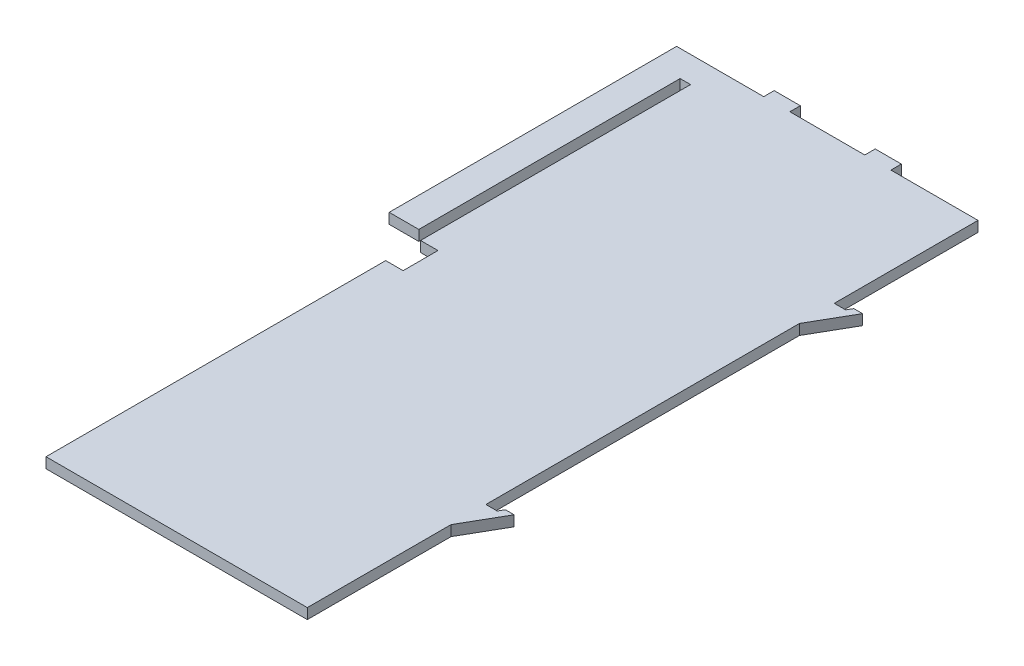
SolidWorks part; units mm, degrees
ref_plane "Front Plane" through (0, 0, 0) normal (0, 0, 1) x (1, 0, 0)
ref_plane "Top Plane" through (0, 0, 0) normal (0, 1, 0) x (1, 0, 0)
ref_plane "Right Plane" through (0, 0, 0) normal (1, 0, 0) x (0, 0, -1)
sketch "Sketch1" plane through (0, 0, 0) normal (0, 1, 0) x (1, 0, 0)
  line L0 (0, 0) -> (0, 165)
  line L3 (173, -220) -> (23, -220)
  line L4 (0, 0) -> (17, 0)
  line L5 (17, 0) -> (17, 150)
  line L6 (17, 150) -> (23, 150)
  line L13 (65, 171) -> (65, 165)
  line L14 (65, 165) -> (108, 165)
  line L15 (108, 165) -> (108, 171)
  line L17 (65, 171) -> (50, 171)
  line L18 (50, 171) -> (50, 165)
  line L19 (50, 165) -> (0, 165)
  line L20 (108, 171) -> (123, 171)
  line L21 (173, 82.5) -> (179.5, 82.5)
  line L22 (123, 171) -> (123, 165)
  line L23 (123, 165) -> (173, 165)
  line L24 (179.5, 82.5) -> (181.225, 85.5)
  line L25 (181.225, 85.5) -> (186.225, 85.5)
  line L26 (186.225, 85.5) -> (173, 62.5)
  line L28 (173, -117.5) -> (179.5, -117.5)
  line L29 (179.5, -117.5) -> (181.225, -114.5)
  line L30 (181.225, -114.5) -> (186.225, -114.5)
  line L31 (186.225, -114.5) -> (173, -137.5)
  line L33 (173, 165) -> (173, 82.5)
  line L34 (173, 62.5) -> (173, -117.5)
  line L35 (173, -137.5) -> (173, -220)
  line L36 (23, -25) -> (33, -25)
  line L37 (33, -25) -> (33, -5)
  line L38 (33, -5) -> (23, -5)
  line L39 (23, 150) -> (23, -5)
  line L40 (23, -25) -> (23, -220)
  dimension "D1" = 6
  dimension "D2" = 15
  dimension "D3" = 150
  dimension "D4" = 370
  dimension "D5" = 150
  dimension "D6" = 17
  dimension "D7" = 15
  dimension "D8" = 195
  dimension "D9" = 10
  dimension "D10" = 50
  dimension "D11" = 6
  dimension "D12" = 6.5
  dimension "D13" = 5
  dimension "D14" = 20
  dimension "D15" = 3
  dimension "D16" = 6.5
  dimension "D17" = 5
  dimension "D18" = 20
  dimension "D19" = 3
  dimension "D20" = 200
  dimension "D21" = 20
extrude "Boss-Extrude1" add sketch "Sketch1" along normal blind 6
